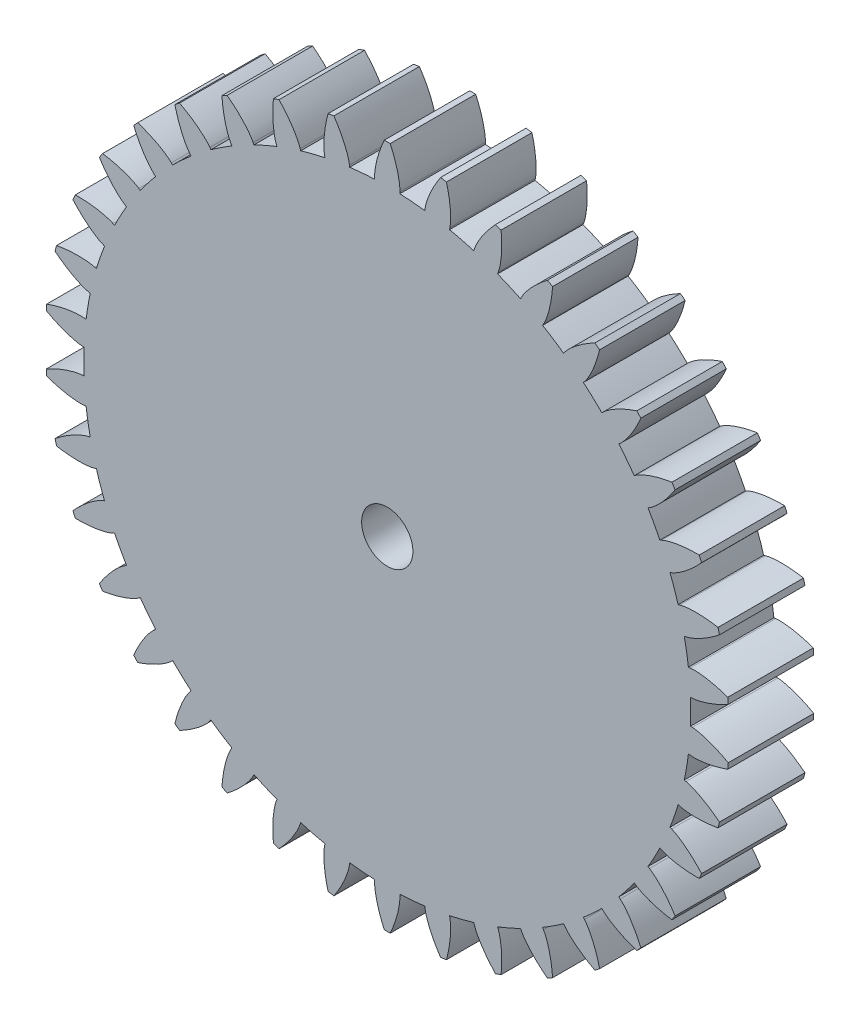
SolidWorks part; units mm, degrees
ref_plane "前视基准面" through (0, 0, 0) normal (0, 0, 1) x (1, 0, 0)
ref_plane "上视基准面" through (0, 0, 0) normal (0, 1, 0) x (1, 0, 0)
ref_plane "右视基准面" through (0, 0, 0) normal (1, 0, 0) x (0, 0, -1)
other "Configuration Table"
sketch "草图1" plane through (0, 0, 0) normal (0, 0, 1) x (1, 0, 0)
  line L0 (0, 0) -> (3, 0) construction
  line L1 (0, 0) -> (2.8978, 0.7765) construction
  line L2 (0, 0) -> (2.7305, 0.701)
  line L3 (2.8978, 0.7765) -> (2.8978, -0.7765) construction
  line L4 (0, 0) -> (2.7305, -0.701)
  circle A0 centre (0, 0) radius 4
  circle A1 centre (0, 0) radius 3 construction
  circle A2 centre (0, 0) radius 1.75
  circle A3 centre (0, 0) radius 2.8191 construction
  circle A4 centre (0, 0) radius 1.5
  spline S0 degree 4 poles (2.7305, 0.701) (2.7514, 0.7063) (2.8083, 0.7255) (2.9105, 0.779) (3.0627, 0.8875) (3.236, 1.0573) (3.4253, 1.3046) (3.6012, 1.6247) (3.742, 2.0003) (3.8364, 2.4221) (3.8779, 2.852) (3.8707, 3.2837) (3.8157, 3.7334) (3.69, 4.2802) (3.4574, 4.9086) (3.0836, 5.5918) (2.5556, 6.2772) (1.9356, 6.8796) (1.2391, 7.3923) (0.4849, 7.8122) (-0.3175, 8.1368) (-1.1468, 8.3674) (-2.0054, 8.5023) (-2.7502, 8.5427) (-3.4127, 8.5171) (-3.8849, 8.4708) (-4.3024, 8.4076) (-4.5772, 8.3558) (-4.9624, 8.2714) (-5.2496, 8.1908) (-5.5362, 8.1071) (-5.6783, 8.056) (-5.7704, 8.0254) knots 0 0 0 0 0 0.005604 0.015718 0.02996 0.048734 0.068727 0.096889 0.125051 0.153212 0.181374 0.209535 0.237696 0.271429 0.327752 0.384075 0.440398 0.496721 0.553044 0.609367 0.66569 0.722013 0.778336 0.834659 0.86282 0.890982 0.909091 0.931818 0.954545 0.977273 1 1 1 1 1 construction
  spline S1 degree 4 poles (2.7305, 0.701) (2.7514, 0.7063) (2.8083, 0.7255) (2.9105, 0.779) (3.0627, 0.8875) (3.236, 1.0573) (3.4253, 1.3046) (3.6012, 1.6247) (3.742, 2.0003) (3.8364, 2.4221) (3.8779, 2.852) (3.8707, 3.2837) (3.8157, 3.7334) (3.69, 4.2802) (3.4574, 4.9086) (3.0836, 5.5918) (2.5556, 6.2772) (1.9356, 6.8796) (1.2391, 7.3923) (0.4849, 7.8122) (-0.3175, 8.1368) (-1.1468, 8.3674) (-2.0054, 8.5023) (-2.7502, 8.5427) (-3.4127, 8.5171) (-3.8849, 8.4708) (-4.2047, 8.4224) (-4.3632, 8.395) (-4.4251, 8.3835) knots 0 0 0 0 0 0.005604 0.015718 0.02996 0.048734 0.068727 0.096889 0.125051 0.153212 0.181374 0.209535 0.237696 0.271429 0.327752 0.384075 0.440398 0.496721 0.553044 0.609367 0.66569 0.722013 0.778336 0.834659 0.86282 0.890982 0.909091 0.909091 0.909091 0.909091 0.909091
  spline S2 degree 4 poles (2.7305, -0.701) (2.7514, -0.7063) (2.8083, -0.7255) (2.9105, -0.779) (3.0627, -0.8875) (3.236, -1.0573) (3.4253, -1.3046) (3.6012, -1.6247) (3.742, -2.0003) (3.8364, -2.4221) (3.8779, -2.852) (3.8707, -3.2837) (3.8157, -3.7334) (3.69, -4.2802) (3.4574, -4.9086) (3.0836, -5.5918) (2.5556, -6.2772) (1.9356, -6.8796) (1.2391, -7.3923) (0.4849, -7.8122) (-0.3175, -8.1368) (-1.1468, -8.3674) (-2.0054, -8.5023) (-2.7502, -8.5427) (-3.4127, -8.5171) (-3.8849, -8.4708) (-4.3024, -8.4076) (-4.5772, -8.3558) (-4.9624, -8.2714) (-5.2496, -8.1908) (-5.5362, -8.1071) (-5.6783, -8.056) (-5.7704, -8.0254) knots 0 0 0 0 0 0.005604 0.015718 0.02996 0.048734 0.068727 0.096889 0.125051 0.153212 0.181374 0.209535 0.237696 0.271429 0.327752 0.384075 0.440398 0.496721 0.553044 0.609367 0.66569 0.722013 0.778336 0.834659 0.86282 0.890982 0.909091 0.931818 0.954545 0.977273 1 1 1 1 1 construction
  spline S3 degree 4 poles (2.7305, -0.701) (2.7514, -0.7063) (2.8083, -0.7255) (2.9105, -0.779) (3.0627, -0.8875) (3.236, -1.0573) (3.4253, -1.3046) (3.6012, -1.6247) (3.742, -2.0003) (3.8364, -2.4221) (3.8779, -2.852) (3.8707, -3.2837) (3.8157, -3.7334) (3.69, -4.2802) (3.4574, -4.9086) (3.0836, -5.5918) (2.5556, -6.2772) (1.9356, -6.8796) (1.2391, -7.3923) (0.4849, -7.8122) (-0.3175, -8.1368) (-1.1468, -8.3674) (-2.0054, -8.5023) (-2.7502, -8.5427) (-3.4127, -8.5171) (-3.8849, -8.4708) (-4.2047, -8.4224) (-4.3632, -8.395) (-4.4251, -8.3835) knots 0 0 0 0 0 0.005604 0.015718 0.02996 0.048734 0.068727 0.096889 0.125051 0.153212 0.181374 0.209535 0.237696 0.271429 0.327752 0.384075 0.440398 0.496721 0.553044 0.609367 0.66569 0.722013 0.778336 0.834659 0.86282 0.890982 0.909091 0.909091 0.909091 0.909091 0.909091
  point P15 (2.8978, 0)
  dimension "齿顶圆直径" = 8
  dimension "分度圆直径" = 6
  dimension "齿根圆直径" = 3.5
  dimension "基圆直径" = 5.6382
  dimension "内孔直径" = 3
  dimension "渐近线镜像线夹角" = 15
extrude "凸台-拉伸1" add sketch "草图1" along normal blind 5 contours A0 | A4
extrude "切除-拉伸1" cut sketch "草图1<3>" along normal through all contours A2 S3 A0 S1 region at (3.0753, 0, 0)
sketch "草图1<3>" plane through (0, 0, 0) normal (0, 0, 1) x (1, 0, 0) same geometry as "草图1"
pattern_circular "阵列(圆周)1" count 6 every 60 about axis through (0, 0, 5) along (0, 0, 1) of "切除-拉伸1"
sketch "草图2" plane through (0, 0, 5) normal (0, 0, 1) x (1, 0, 0)
  line L0 (0, 0) -> (19, 0) construction
  line L1 (0, 0) -> (17.8389, 0.7378)
  line L2 (0, 0) -> (17.8389, -0.7378)
  line L3 (17.8389, 0.7378) -> (17.8389, -0.7378) construction
  circle A0 centre (0, 0) radius 19 construction
  circle A1 centre (0, 0) radius 17.8542 construction
  circle A2 centre (0, 0) radius 17.75
  circle A3 centre (0, 0) radius 20
  circle A4 centre (0, 0) radius 1.5
  spline S0 degree 4 poles (17.8389, -0.7378) (17.8728, -0.7392) (17.9406, -0.7441) (18.0752, -0.7621) (18.3288, -0.8123) (18.6635, -0.9051) (19.1205, -1.0702) (19.658, -1.3153) (20.4669, -1.7609) (21.5195, -2.5027) (22.8507, -3.7145) (24.3091, -5.5094) (25.6114, -7.6908) (26.6766, -10.2121) (27.4216, -12.8444) (27.8645, -15.543) (28.0306, -18.4074) (27.8656, -21.9567) (27.1273, -26.1356) (25.5694, -30.8158) (23.0564, -35.6845) (20.2692, -39.5823) (17.5235, -42.6283) (15.0272, -44.9572) (12.9164, -46.6904) (10.7035, -48.2904) (8.3975, -49.7545) (5.4145, -51.4121) (1.6874, -53.1227) (-2.8247, -54.7082) (-7.1558, -55.7237) (-10.5228, -56.2445) (-12.9095, -56.489) (-14.244, -56.5948) (-15.5428, -56.66) (-16.5612, -56.6949) (-17.638, -56.7056) (-18.2041, -56.705) (-18.894, -56.6964) (-19.4423, -56.6837) (-20.126, -56.6612) (-20.9547, -56.6234) (-21.9141, -56.5638) (-23.0135, -56.4746) (-24.1084, -56.3645) (-25.2027, -56.2336) (-26.0203, -56.1199) (-26.5651, -56.0373) (-26.8369, -55.9943) knots 0 0 0 0 0 0.001401 0.002802 0.005604 0.010661 0.015718 0.022839 0.02996 0.048734 0.068727 0.096889 0.125051 0.153212 0.181374 0.209535 0.237696 0.271429 0.327752 0.384075 0.440398 0.496721 0.524883 0.553044 0.581206 0.609367 0.637529 0.66569 0.722013 0.778336 0.834659 0.84874 0.86282 0.876901 0.890982 0.900036 0.909091 0.914773 0.920455 0.926136 0.931818 0.943182 0.954545 0.965909 0.977273 0.988636 1 1 1 1 1 construction
  spline S1 degree 4 poles (17.8389, -0.7378) (17.8728, -0.7392) (17.9406, -0.7441) (18.0752, -0.7621) (18.3288, -0.8123) (18.6635, -0.9051) (19.1205, -1.0702) (19.658, -1.3153) (20.4669, -1.7609) (21.5195, -2.5027) (22.8507, -3.7145) (24.3091, -5.5094) (25.6114, -7.6908) (26.6766, -10.2121) (27.4216, -12.8444) (27.8645, -15.543) (28.0306, -18.4074) (27.8656, -21.9567) (27.1273, -26.1356) (25.5694, -30.8158) (23.0564, -35.6845) (20.2692, -39.5823) (17.5235, -42.6283) (15.0272, -44.9572) (12.9164, -46.6904) (10.7035, -48.2904) (8.3975, -49.7545) (5.4145, -51.4121) (1.6874, -53.1227) (-2.8247, -54.7082) (-7.1558, -55.7237) (-10.5228, -56.2445) (-12.9095, -56.489) (-14.244, -56.5948) (-15.5428, -56.66) (-16.5612, -56.6949) (-17.4764, -56.704) (-17.8641, -56.7049) (-18.0636, -56.7042) knots 0 0 0 0 0 0.001401 0.002802 0.005604 0.010661 0.015718 0.022839 0.02996 0.048734 0.068727 0.096889 0.125051 0.153212 0.181374 0.209535 0.237696 0.271429 0.327752 0.384075 0.440398 0.496721 0.524883 0.553044 0.581206 0.609367 0.637529 0.66569 0.722013 0.778336 0.834659 0.84874 0.86282 0.876901 0.890982 0.900036 0.909091 0.909091 0.909091 0.909091 0.909091
  spline S2 degree 4 poles (17.8389, 0.7378) (17.8728, 0.7392) (17.9406, 0.7441) (18.0752, 0.7621) (18.3288, 0.8123) (18.6635, 0.9051) (19.1205, 1.0702) (19.658, 1.3153) (20.4669, 1.7609) (21.5195, 2.5027) (22.8507, 3.7145) (24.3091, 5.5094) (25.6114, 7.6908) (26.6766, 10.2121) (27.4216, 12.8444) (27.8645, 15.543) (28.0306, 18.4074) (27.8656, 21.9567) (27.1273, 26.1356) (25.5694, 30.8158) (23.0564, 35.6845) (20.2692, 39.5823) (17.5235, 42.6283) (15.0272, 44.9572) (12.9164, 46.6904) (10.7035, 48.2904) (8.3975, 49.7545) (5.4145, 51.4121) (1.6874, 53.1227) (-2.8247, 54.7082) (-7.1558, 55.7237) (-10.5228, 56.2445) (-12.9095, 56.489) (-14.244, 56.5948) (-15.5428, 56.66) (-16.5612, 56.6949) (-17.638, 56.7056) (-18.2041, 56.705) (-18.894, 56.6964) (-19.4423, 56.6837) (-20.126, 56.6612) (-20.9547, 56.6234) (-21.9141, 56.5638) (-23.0135, 56.4746) (-24.1084, 56.3645) (-25.2027, 56.2336) (-26.0203, 56.1199) (-26.5651, 56.0373) (-26.8369, 55.9943) knots 0 0 0 0 0 0.001401 0.002802 0.005604 0.010661 0.015718 0.022839 0.02996 0.048734 0.068727 0.096889 0.125051 0.153212 0.181374 0.209535 0.237696 0.271429 0.327752 0.384075 0.440398 0.496721 0.524883 0.553044 0.581206 0.609367 0.637529 0.66569 0.722013 0.778336 0.834659 0.84874 0.86282 0.876901 0.890982 0.900036 0.909091 0.914773 0.920455 0.926136 0.931818 0.943182 0.954545 0.965909 0.977273 0.988636 1 1 1 1 1 construction
  spline S3 degree 4 poles (17.8389, 0.7378) (17.8728, 0.7392) (17.9406, 0.7441) (18.0752, 0.7621) (18.3288, 0.8123) (18.6635, 0.9051) (19.1205, 1.0702) (19.658, 1.3153) (20.4669, 1.7609) (21.5195, 2.5027) (22.8507, 3.7145) (24.3091, 5.5094) (25.6114, 7.6908) (26.6766, 10.2121) (27.4216, 12.8444) (27.8645, 15.543) (28.0306, 18.4074) (27.8656, 21.9567) (27.1273, 26.1356) (25.5694, 30.8158) (23.0564, 35.6845) (20.2692, 39.5823) (17.5235, 42.6283) (15.0272, 44.9572) (12.9164, 46.6904) (10.7035, 48.2904) (8.3975, 49.7545) (5.4145, 51.4121) (1.6874, 53.1227) (-2.8247, 54.7082) (-7.1558, 55.7237) (-10.5228, 56.2445) (-12.9095, 56.489) (-14.244, 56.5948) (-15.5428, 56.66) (-16.5612, 56.6949) (-17.4764, 56.704) (-17.8641, 56.7049) (-18.0636, 56.7042) knots 0 0 0 0 0 0.001401 0.002802 0.005604 0.010661 0.015718 0.022839 0.02996 0.048734 0.068727 0.096889 0.125051 0.153212 0.181374 0.209535 0.237696 0.271429 0.327752 0.384075 0.440398 0.496721 0.524883 0.553044 0.581206 0.609367 0.637529 0.66569 0.722013 0.778336 0.834659 0.84874 0.86282 0.876901 0.890982 0.900036 0.909091 0.909091 0.909091 0.909091 0.909091
  point P16 (17.8389, 0)
  dimension "内孔直径" = 3
  dimension "分度圆直径" = 38
  dimension "齿顶圆直径" = 40
  dimension "基圆直径" = 35.7083
  dimension "齿根圆直径" = 35.5
  dimension "渐开线镜像线夹角" = 2.368
extrude "凸台-拉伸2" add sketch "草图2" along normal blind 5 contours A3 | A4
extrude "切除-拉伸3" cut sketch "草图2<3>" along normal through all contours S3 L1 A2 L2 S1 A3 region at (19.0065, 0, 5)
sketch "草图2<3>" plane through (0, 0, 5) normal (0, 0, 1) x (1, 0, 0) same geometry as "草图2"
pattern_circular "阵列(圆周)2" count 38 over 360 about axis through (0, 0, 10) along (0, 0, 1) of "切除-拉伸3"
equation "\"m\"= 1'模数"
equation "\"z\"= 6'齿数"
equation "\"a\"= 20度'压力角"
equation "\"d\"= \"m\" * \"z\"'分度圆直径"
equation "\"da\"= ( \"z\" + 2 ) * \"m\"'齿顶圆直径"
equation "\"df\"= ( \"z\" - 2.5 ) * \"m\"'齿根圆直径"
equation "\"s\"= 0.5 * PI * \"m\"'分度圆齿厚"
equation "\"r\"= 0.38 * \"m\"'齿根圆角"
equation "\"B\"= 0.3 * \"d\"'齿厚"
equation "\"db\"= \"m\" * \"z\" * cos ( \"a\" )'基圆直径"
equation "\"rb\"= \"db\" / 2'基圆半径"
equation "\"齿顶圆直径@草图1\"= \"da\""
equation "\"分度圆直径@草图1\"= \"d\""
equation "\"齿根圆直径@草图1\"= \"df\""
equation "\"基圆直径@草图1\"= \"db\""
equation "\"渐近线镜像线夹角@草图1\"= 360 / 4 / \"z\""
equation "\"h\"= 5'齿轮厚度"
equation "\"ir\"= 3'内孔直径"
equation "\"内孔直径@草图1\"= \"ir\""
equation "\"齿轮厚@凸台-拉伸1\"= \"h\""
equation "\"齿轮夹角@阵列(圆周)1\"= 360 / \"z\""
equation "\"齿数@阵列(圆周)1\"= \"z\""
equation "\"m1\"= 1'模数"
equation "\"z1\"= 38'齿数"
equation "\"a1\"= 20度'压力角"
equation "\"d1\"= \"m1\" * \"z1\"'分度圆直径"
equation "\"da1\"= ( \"z1\" + 2 ) * \"m1\"'齿顶圆直径"
equation "\"df1\"= ( \"z1\" - 2.5 ) * \"m1\"'齿根圆直径"
equation "\"s1\"= 0.5 * PI * \"m1\"'分度圆齿厚"
equation "\"r1\"= 0.38 * \"m1\"'齿根圆角"
equation "\"B1\"= 0.3 * \"d1\"'齿厚"
equation "\"db1\"= \"m1\" * \"z1\" * cos ( \"a1\" )'基圆直径"
equation "\"rb1\"= \"db1\" / 2'基圆半径"
equation "\"分度圆直径@草图2\"= \"d1\""
equation "\"齿顶圆直径@草图2\"= \"da1\""
equation "\"基圆直径@草图2\"= \"db1\""
equation "\"齿根圆直径@草图2\"= \"df1\""
equation "\"渐开线镜像线夹角@草图2\"= 360 / 4 / \"z1\""
equation "\"内孔直径@草图2\"= \"ir\""
equation "\"二层齿轮厚@凸台-拉伸2\" = \"h1\""
equation "\"h1\"= 5'齿轮厚度"
equation "\"二层齿数@阵列(圆周)2\"= \"z1\""
